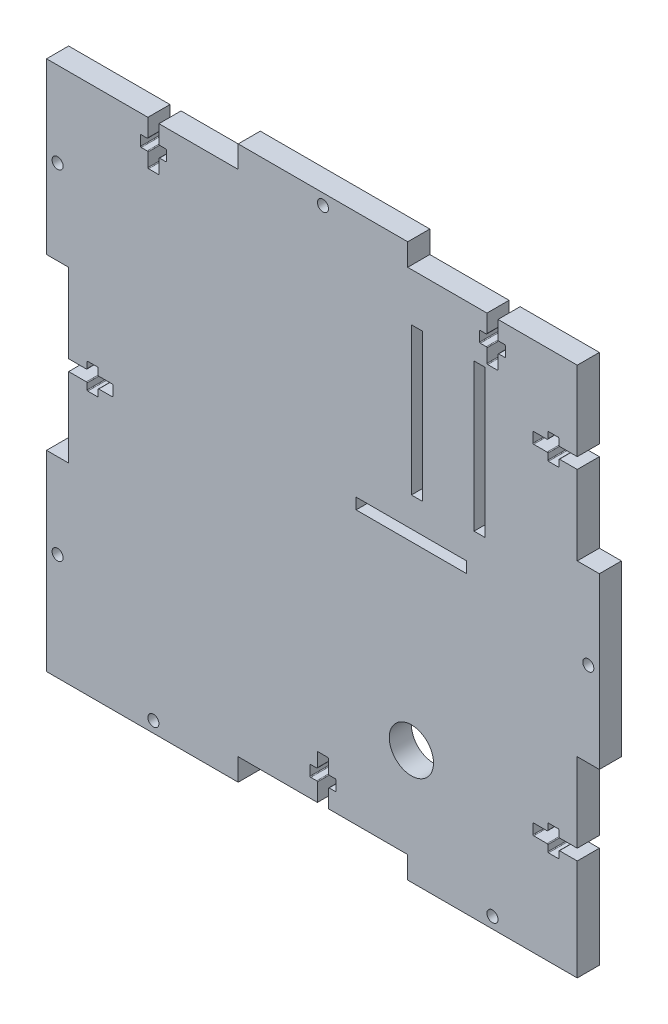
SolidWorks part; units mm, degrees
ref_plane "Front Plane" through (0, 0, 0) normal (0, 0, 1) x (1, 0, 0)
ref_plane "Top Plane" through (0, 0, 0) normal (0, 1, 0) x (1, 0, 0)
ref_plane "Right Plane" through (0, 0, 0) normal (1, 0, 0) x (0, 0, -1)
sketch "Sketch1" plane through (0, 0, 0) normal (0, 0, 1) x (1, 0, 0)
  line L0 (-69, 69) -> (-23, 69)
  line L5 (-75, -75) -> (75, -75) construction
  line L6 (-75, -75) -> (-75, 75) construction
  line L7 (-75, 75) -> (75, 75) construction
  line L8 (75, -75) -> (75, 75) construction
  line L9 (75, 23) -> (69, 23)
  line L10 (69, -23) -> (75, -23)
  line L11 (-69, -69) -> (69, -69) construction
  line L12 (-69, -69) -> (-69, 69) construction
  line L13 (-69, 69) -> (69, 69) construction
  line L14 (69, -69) -> (69, 69) construction
  line L15 (-69, -69) -> (69, 69) construction
  line L16 (69, -69) -> (69, -23)
  line L17 (-23, 69) -> (-23, 75)
  line L18 (-23, 75) -> (23, 75)
  line L19 (23, 75) -> (23, 69)
  line L20 (23, 69) -> (69, 69)
  line L21 (75, -23) -> (75, 23)
  line L22 (69, 23) -> (69, 69)
  line L23 (-75, 23) -> (-69, 23)
  line L24 (-69, 69) -> (-75, 69)
  line L25 (-75, 69) -> (-75, 23)
  line L26 (69, -69) -> (69, -75)
  line L27 (69, -75) -> (23, -75)
  line L28 (23, -75) -> (23, -69)
  line L29 (23, -69) -> (-23, -69)
  line L30 (-23, -69) -> (-23, -75)
  line L31 (-23, -75) -> (-69, -75)
  line L32 (-69, -75) -> (-69, -69) construction
  line L33 (-69, 23) -> (-69, -23)
  line L34 (-69, -23) -> (-75, -23)
  line L35 (-75, -23) -> (-75, -69)
  line L36 (-75, -69) -> (-69, -69) construction
  line L37 (-46, 69) -> (-46, -75) construction
  line L38 (-69, 69) -> (69, -69) construction
  line L39 (-75, -75) -> (-69, -75)
  line L40 (-75, -75) -> (-75, -69)
  point P0 (0, 0)
  point P6 (-7, -7)
  point P26 (0, -75)
  point P27 (-75, 0)
  dimension "D1" = 150
  dimension "D2" = 150
  dimension "D5" = 46
  dimension "D3" = 6
  dimension "D6" = 6
  dimension "D7" = 6
extrude "Box Side" add sketch "Sketch1" along normal blind 6
sketch "Sketch2" plane through (0, 0, 6) normal (0, 0, 1) x (1, 0, 0)
  line L0 (23, 72) -> (-23, 72) construction
  line L1 (23, 75) -> (23, 69) construction
  line L2 (-23, 69) -> (-23, 75) construction
  line L3 (-46, 69) -> (-46, -75) construction
  line L5 (0, 75) -> (0, 69) construction
  line L6 (-23, 75) -> (23, 75) construction
  line L7 (-69, 69) -> (69, 69) construction
  line L16 (-46, 69) -> (-46, -75) construction
  line L21 (0, -69) -> (0, 69) construction
  line L35 (-69, 69) -> (-23, 69) construction
  line L36 (-44.5, 69) -> (-44.5, 64.2)
  line L37 (-44.3, 64) -> (-42.7, 64)
  line L38 (-42.5, 63.8) -> (-42.5, 61.2)
  line L39 (-42.7, 61) -> (-44.3, 61)
  line L40 (-44.5, 60.8) -> (-44.5, 57.2)
  line L46 (-44.7, 57) -> (-47.3, 57)
  line L48 (-44.5, 69) -> (-47.5, 69)
  line L51 (-47.5, 60.8) -> (-47.5, 57.2)
  line L52 (-49.3, 61) -> (-47.7, 61)
  line L53 (-49.5, 63.8) -> (-49.5, 61.2)
  line L54 (-47.7, 64) -> (-49.3, 64)
  line L55 (-47.5, 69) -> (-47.5, 64.2)
  line L56 (47.5, 69) -> (47.5, 64.2)
  line L57 (47.7, 64) -> (49.3, 64)
  line L58 (49.5, 63.8) -> (49.5, 61.2)
  line L59 (49.3, 61) -> (47.7, 61)
  line L60 (47.5, 60.8) -> (47.5, 57.2)
  line L61 (44.5, 69) -> (47.5, 69)
  line L62 (44.7, 57) -> (47.3, 57)
  line L63 (44.5, 60.8) -> (44.5, 57.2)
  line L64 (42.7, 61) -> (44.3, 61)
  line L65 (42.5, 63.8) -> (42.5, 61.2)
  line L66 (44.3, 64) -> (42.7, 64)
  line L67 (44.5, 69) -> (44.5, 64.2)
  line L68 (-69, -69) -> (69, 69) construction
  line L69 (-69, -69) -> (69, 69) construction
  line L70 (75, 0) -> (69, 0) construction
  line L71 (72, 23) -> (72, -23) construction
  line L72 (69, 44.5) -> (64.2, 44.5)
  line L73 (64, 44.3) -> (64, 42.7)
  line L74 (63.8, 42.5) -> (61.2, 42.5)
  line L75 (61, 42.7) -> (61, 44.3)
  line L76 (60.8, 44.5) -> (57.2, 44.5)
  line L77 (57, 44.7) -> (57, 47.3)
  line L78 (69, 44.5) -> (69, 47.5)
  line L79 (60.8, 47.5) -> (57.2, 47.5)
  line L80 (61, 49.3) -> (61, 47.7)
  line L81 (63.8, 49.5) -> (61.2, 49.5)
  line L82 (64, 47.7) -> (64, 49.3)
  line L83 (69, 47.5) -> (64.2, 47.5)
  line L84 (69, -47.5) -> (64.2, -47.5)
  line L85 (64, -47.7) -> (64, -49.3)
  line L86 (63.8, -49.5) -> (61.2, -49.5)
  line L87 (61, -49.3) -> (61, -47.7)
  line L88 (60.8, -47.5) -> (57.2, -47.5)
  line L89 (69, -44.5) -> (69, -47.5)
  line L90 (57, -44.7) -> (57, -47.3)
  line L91 (60.8, -44.5) -> (57.2, -44.5)
  line L92 (61, -42.7) -> (61, -44.3)
  line L93 (63.8, -42.5) -> (61.2, -42.5)
  line L94 (64, -44.3) -> (64, -42.7)
  line L95 (69, -44.5) -> (64.2, -44.5)
  line L120 (-69, 69) -> (69, -69) construction
  line L121 (-69, 69) -> (69, -69) construction
  line L122 (-1.5, -69) -> (1.5, -69)
  line L123 (-23, -69) -> (23, -69) construction
  line L124 (1.5, -69) -> (1.5, -64.2)
  line L125 (1.7, -64) -> (3.3, -64)
  line L126 (3.5, -63.8) -> (3.5, -61.2)
  line L127 (3.3, -61) -> (1.7, -61)
  line L128 (1.5, -60.8) -> (1.5, -57.2)
  line L129 (1.3, -57) -> (-1.3, -57)
  line L130 (-1.5, -60.8) -> (-1.5, -57.2)
  line L131 (-3.3, -61) -> (-1.7, -61)
  line L132 (-3.5, -63.8) -> (-3.5, -61.2)
  line L133 (-1.7, -64) -> (-3.3, -64)
  line L134 (-1.5, -69) -> (-1.5, -64.2)
  line L135 (-69, -1.5) -> (-64.2, -1.5)
  line L136 (-64, -1.7) -> (-64, -3.3)
  line L137 (-63.8, -3.5) -> (-61.2, -3.5)
  line L138 (-61, -3.3) -> (-61, -1.7)
  line L139 (-60.8, -1.5) -> (-57.2, -1.5)
  line L140 (-57, 1.3) -> (-57, -1.3)
  line L141 (-60.8, 1.5) -> (-57.2, 1.5)
  line L142 (-61, 3.3) -> (-61, 1.7)
  line L143 (-63.8, 3.5) -> (-61.2, 3.5)
  line L144 (-64, 1.7) -> (-64, 3.3)
  line L145 (-69, 1.5) -> (-64.2, 1.5)
  line L146 (-69, -1.5) -> (-69, 1.5)
  line L147 (-69, -72) -> (-23, -72) construction
  line L148 (-23, 69) -> (-75, 69) construction
  line L149 (-23, -75) -> (-23, -69) construction
  line L150 (-69, -69) -> (-69, -75) construction
  line L151 (-75, -75) -> (-23, -75) construction
  circle A0 centre (0, 72) radius 1.5
  arc A1 (-44.5, 57.2) -> (-44.7, 57) centre (-44.7, 57.2) cw
  arc A2 (-44.3, 61) -> (-44.5, 60.8) centre (-44.3, 60.8) ccw
  arc A3 (-42.5, 61.2) -> (-42.7, 61) centre (-42.7, 61.2) cw
  arc A4 (-42.7, 64) -> (-42.5, 63.8) centre (-42.7, 63.8) cw
  arc A5 (-44.5, 64.2) -> (-44.3, 64) centre (-44.3, 64.2) ccw
  arc A6 (-47.5, 64.2) -> (-47.7, 64) centre (-47.7, 64.2) cw
  arc A7 (-49.3, 64) -> (-49.5, 63.8) centre (-49.3, 63.8) ccw
  arc A8 (-49.5, 61.2) -> (-49.3, 61) centre (-49.3, 61.2) ccw
  arc A9 (-47.7, 61) -> (-47.5, 60.8) centre (-47.7, 60.8) cw
  arc A10 (-47.5, 57.2) -> (-47.3, 57) centre (-47.3, 57.2) ccw
  arc A11 (47.5, 57.2) -> (47.3, 57) centre (47.3, 57.2) cw
  arc A12 (47.7, 61) -> (47.5, 60.8) centre (47.7, 60.8) ccw
  arc A13 (49.5, 61.2) -> (49.3, 61) centre (49.3, 61.2) cw
  arc A14 (49.3, 64) -> (49.5, 63.8) centre (49.3, 63.8) cw
  arc A15 (47.5, 64.2) -> (47.7, 64) centre (47.7, 64.2) ccw
  arc A16 (44.5, 64.2) -> (44.3, 64) centre (44.3, 64.2) cw
  arc A17 (42.7, 64) -> (42.5, 63.8) centre (42.7, 63.8) ccw
  arc A18 (42.5, 61.2) -> (42.7, 61) centre (42.7, 61.2) ccw
  arc A19 (44.3, 61) -> (44.5, 60.8) centre (44.3, 60.8) cw
  arc A20 (44.5, 57.2) -> (44.7, 57) centre (44.7, 57.2) ccw
  arc A21 (57.2, 44.5) -> (57, 44.7) centre (57.2, 44.7) cw
  arc A22 (61, 44.3) -> (60.8, 44.5) centre (60.8, 44.3) ccw
  arc A23 (61.2, 42.5) -> (61, 42.7) centre (61.2, 42.7) cw
  arc A24 (64, 42.7) -> (63.8, 42.5) centre (63.8, 42.7) cw
  arc A25 (64.2, 44.5) -> (64, 44.3) centre (64.2, 44.3) ccw
  arc A26 (64.2, 47.5) -> (64, 47.7) centre (64.2, 47.7) cw
  arc A27 (64, 49.3) -> (63.8, 49.5) centre (63.8, 49.3) ccw
  arc A28 (61.2, 49.5) -> (61, 49.3) centre (61.2, 49.3) ccw
  arc A29 (61, 47.7) -> (60.8, 47.5) centre (60.8, 47.7) cw
  arc A30 (57.2, 47.5) -> (57, 47.3) centre (57.2, 47.3) ccw
  arc A31 (57.2, -47.5) -> (57, -47.3) centre (57.2, -47.3) cw
  arc A32 (61, -47.7) -> (60.8, -47.5) centre (60.8, -47.7) ccw
  arc A33 (61.2, -49.5) -> (61, -49.3) centre (61.2, -49.3) cw
  arc A34 (64, -49.3) -> (63.8, -49.5) centre (63.8, -49.3) cw
  arc A35 (64.2, -47.5) -> (64, -47.7) centre (64.2, -47.7) ccw
  arc A36 (64.2, -44.5) -> (64, -44.3) centre (64.2, -44.3) cw
  arc A37 (64, -42.7) -> (63.8, -42.5) centre (63.8, -42.7) ccw
  arc A38 (61.2, -42.5) -> (61, -42.7) centre (61.2, -42.7) ccw
  arc A39 (61, -44.3) -> (60.8, -44.5) centre (60.8, -44.3) cw
  arc A40 (57.2, -44.5) -> (57, -44.7) centre (57.2, -44.7) ccw
  circle A41 centre (72, 0) radius 1.5
  arc A62 (1.5, -57.2) -> (1.3, -57) centre (1.3, -57.2) ccw
  arc A63 (1.7, -61) -> (1.5, -60.8) centre (1.7, -60.8) cw
  arc A64 (3.5, -61.2) -> (3.3, -61) centre (3.3, -61.2) ccw
  arc A65 (3.3, -64) -> (3.5, -63.8) centre (3.3, -63.8) ccw
  arc A66 (1.5, -64.2) -> (1.7, -64) centre (1.7, -64.2) cw
  arc A67 (-1.5, -64.2) -> (-1.7, -64) centre (-1.7, -64.2) ccw
  arc A68 (-3.3, -64) -> (-3.5, -63.8) centre (-3.3, -63.8) cw
  arc A69 (-3.5, -61.2) -> (-3.3, -61) centre (-3.3, -61.2) cw
  arc A70 (-1.7, -61) -> (-1.5, -60.8) centre (-1.7, -60.8) ccw
  arc A71 (-1.5, -57.2) -> (-1.3, -57) centre (-1.3, -57.2) cw
  arc A72 (-57.2, -1.5) -> (-57, -1.3) centre (-57.2, -1.3) ccw
  arc A73 (-61, -1.7) -> (-60.8, -1.5) centre (-60.8, -1.7) cw
  arc A74 (-61.2, -3.5) -> (-61, -3.3) centre (-61.2, -3.3) ccw
  arc A75 (-64, -3.3) -> (-63.8, -3.5) centre (-63.8, -3.3) ccw
  arc A76 (-64.2, -1.5) -> (-64, -1.7) centre (-64.2, -1.7) cw
  arc A77 (-64.2, 1.5) -> (-64, 1.7) centre (-64.2, 1.7) ccw
  arc A78 (-64, 3.3) -> (-63.8, 3.5) centre (-63.8, 3.3) cw
  arc A79 (-61.2, 3.5) -> (-61, 3.3) centre (-61.2, 3.3) cw
  arc A80 (-61, 1.7) -> (-60.8, 1.5) centre (-60.8, 1.7) ccw
  arc A81 (-57.2, 1.5) -> (-57, 1.3) centre (-57.2, 1.3) cw
  circle A82 centre (-46, -72) radius 1.5
  circle A83 centre (46, -72) radius 1.5
  circle A84 centre (-72, 46) radius 1.5
  circle A85 centre (-72, -46) radius 1.5
  point P6 (0, 72)
  point P38 (0, 0)
  point P56 (-46, 57)
  point P88 (46, 57)
  point P161 (57, 46)
  point P162 (57, -46)
  point P198 (0, -57)
  point P231 (-57, 0)
  point P234 (-42.5, 62.5)
  dimension "D1" = 3
  dimension "D2" = 0.2
  dimension "D8" = 0.2
  dimension "D14" = 3
  dimension "D4" = 3
  dimension "D7" = 1.5
  dimension "D10" = 3
  dimension "D12" = 1.5
  dimension "D9" = 12
  dimension "D11" = 5
  dimension "D13" = 7
  dimension "D3" = 12
  dimension "D5" = 7
  dimension "D6" = 5
extrude "Screw Cut-outs" cut sketch "Sketch2" against normal through all
sketch "Bearing Hole" plane through (0, 0, 6) normal (0, 0, 1) x (1, 0, 0)
  line L0 (20, -69) -> (50020, -69) construction
  line L1 (69, -44.5) -> (69, -23) construction
  line L4 (24, -41) -> (50024, -41) construction
  line L5 (24.5774, -47) -> (50024.5774, -47) construction
  line L8 (27, -52) -> (27, -50052) construction
  circle A0 centre (24, -44) radius 3 construction
  circle A1 centre (24, -54) radius 15 construction
  circle A2 centre (24, -44) radius 6
  dimension "D2" = 6
  dimension "D4" = 30
  dimension "D5" = 12
  dimension "D1" = 7
  dimension "D3" = 45
extrude "Shaft Hole" cut sketch "Bearing Hole" against normal through all
sketch "Sketch4" plane through (0, 0, 0) normal (0, 0, -1) x (-1, 0, 0)
  line L0 (-72, 1.5) -> (49928, 1.5) construction
  line L1 (-39, 8) -> (-9, 8)
  line L2 (-39, 8) -> (-39, 5)
  line L3 (-39, 5) -> (-9, 5)
  line L4 (-9, 8) -> (-9, 5)
  line L5 (-75, -23) -> (-75, 23) construction
  line L6 (-69, 23) -> (-69, 44.5) construction
  line L7 (-44, 56) -> (-41, 56)
  line L8 (-44, 56) -> (-44, 16)
  line L9 (-44, 16) -> (-41, 16)
  line L10 (-41, 56) -> (-41, 16)
  line L11 (-27, 56) -> (-24, 56)
  line L12 (-27, 56) -> (-27, 16)
  line L13 (-27, 16) -> (-24, 16)
  line L14 (-24, 56) -> (-24, 16)
  line L15 (-44.5, 69) -> (-23, 69) construction
  circle A1 centre (-72, 0) radius 1.5 construction
  point P18 (-27, 36)
  point P23 (0, 0)
  point P24 (0, 0)
  dimension "D1" = 3.5
  dimension "D2" = 30
  dimension "D3" = 3
  dimension "D4" = 36
  dimension "D5" = 14
  dimension "D6" = 25
  dimension "D7" = 13
  dimension "D8" = 3
  dimension "D9" = 40
extrude "Grooves" cut sketch "Sketch4" against normal up to surface (6 mm away) up to face at (30, -44, 6)
equation "\"filletRadius\"=0.2"
equation "\"D8@Sketch2\"=\"filletRadius\""
equation "\"D2@Sketch2\"=\"filletRadius\""
equation "\"fingerWidth\"= 46"
equation "\"D5@Sketch1\"=\"fingerWidth\""
equation "\"wallThickness\"= 6"
equation "\"D3@Sketch1\" = \"wallThickness\""
equation "\"D6@Sketch1\" = \"wallThickness\""
equation "\"D7@Sketch1\" = \"wallThickness\""
equation "\"D1@Box Side\" = \"wallThickness\""
equation "\"M3\"= 3"
equation "\"D14@Sketch2\"=\"M3\""
equation "\"D1@Sketch2\"=\"M3\""
equation "\"D12@Sketch2\"=\"M3\"/2"
equation "\"nutThickness\"=3"
equation "\"D10@Sketch2\" = \"nutThickness\""
equation "\"boltLength\"= 12"
equation "\"D9@Sketch2\" = \"boltLength\""
equation "\"distanceToNut\"= 5"
equation "\"D11@Sketch2\" = \"distanceToNut\""
equation "\"D13@Sketch2\" = \"nutWidth\""
equation "\"D7@Sketch2\"=\"M3\"/2"
equation "\"D4@Sketch2\" = \"nutThickness\""
equation "\"D3@Sketch2\" = \"boltLength\""
equation "\"D5@Sketch2\" = \"nutWidth\""
equation "\"D6@Sketch2\" = \"distanceToNut\""
equation "\"sideLength\"=150"
equation "\"D1@Sketch1\"=\"sideLength\""
equation "\"D2@Sketch1\"=\"sideLength\""
equation "\"nutWidth\"=7"
